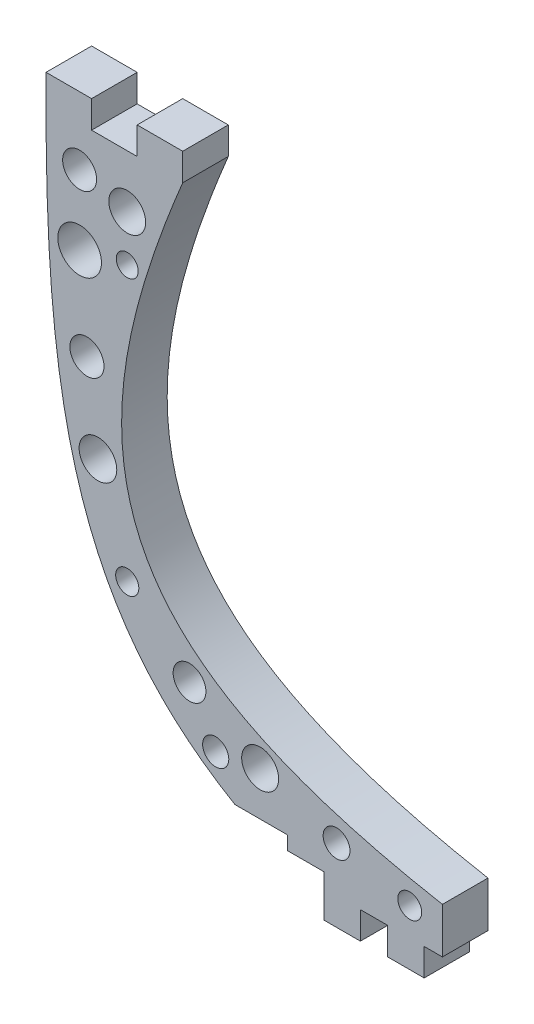
SolidWorks part; units mm, degrees
ref_plane "Plan de face" through (0, 0, 0) normal (0, 0, 1) x (1, 0, 0)
ref_plane "Plan de dessus" through (0, 0, 0) normal (0, 1, 0) x (1, 0, 0)
ref_plane "Plan de droite" through (0, 0, 0) normal (1, 0, 0) x (0, 0, -1)
sketch "Esquisse3" plane through (0, 0, 0) normal (0, 0, 1) x (1, 0, 0)
  line L0 (-7.5, 57.73) -> (-7.5, 0) construction
  line L1 (7.5, 57.73) -> (7.5, 17.682) construction
  line L2 (30, -4.6) -> (30, -1.6)
  line L3 (34, -4.6) -> (30, -4.6)
  line L4 (30, -1.6) -> (27, -1.6)
  line L5 (27, -1.6) -> (27, -4.6)
  line L6 (27, 0) -> (-7.5, 0) construction
  line L7 (7.5, 17.682) -> (36, 3.4) construction
  line L8 (34, -4.6) -> (34, -1.6)
  line L9 (34, -1.6) -> (36, -1.6)
  line L10 (36, -1.6) -> (36, 3.4)
  line L11 (27, -4.6) -> (23, -4.6)
  line L12 (16, 0) -> (-7.5, 11.7764) construction
  line L13 (-7.5, 11.7764) -> (-7.5, 57.73) construction
  line L14 (23, -4.6) -> (23, 0)
  line L15 (-7.5, 93.6282) -> (-7.5, 21.7981) construction
  line L16 (0.2936, 7.8708) -> (32.1661, -8.1012) construction
  line L17 (23, 0) -> (16, 0)
  circle A0 centre (-3.8151, 53.3093) radius 1.8639
  circle A1 centre (1.412, 51.9307) radius 2.0235
  circle A2 centre (-3.8151, 45.6697) radius 2.394
  circle A3 centre (1.412, 46.8759) radius 1.2063
  circle A4 centre (-3.0109, 35.9622) radius 1.8701
  circle A5 centre (-1.8047, 26.8291) radius 2.0679
  circle A6 centre (1.412, 16.777) radius 1.2715
  circle A7 centre (8.2475, 10.6309) radius 1.7991
  circle A8 centre (11.1195, 5.4612) radius 1.436
  circle A9 centre (16, 6.3228) radius 2.0318
  circle A10 centre (24.3837, 3.4) radius 1.4725
  circle A11 centre (32.4136, 1.4916) radius 1.3116
  spline S0 degree 3 poles (16, 0) (-3.9203, 9.9825) (-7.5, 27.8008) (-7.5, 57.73) knots 0 0 0 0 1 1 1 1
  spline S1 degree 3 poles (36, 3.4) (-1.2755, 10.2128) (-5.5671, 26.4267) (7.5, 57.73) knots 0 0 0 0 1 1 1 1
  point P45 (0, 0)
  point P46 (21.2334, 4.0781)
  point P47 (16, -0.1603)
  point P48 (17.1268, 2.4748)
  point P49 (24.3837, 3.4)
  point P50 (19.7989, 3.4)
  point P51 (32.4136, 1.4916)
  line B0 (0, 57.73) -> (0, 44.4605) construction
  line B1 (0, 57.73) -> (2.5, 57.73)
  line B2 (2.5, 60.73) -> (7.5, 60.73)
  line B3 (7.5, 60.73) -> (7.5, 57.73)
  line B4 (2.5, 60.73) -> (2.5, 57.73)
  line B5 (0, 57.73) -> (-2.5, 57.73)
  line B6 (-2.5, 57.73) -> (-2.5, 60.73)
  line B7 (-2.5, 60.73) -> (-7.5, 60.73)
  line B8 (-7.5, 60.73) -> (-7.5, 57.73)
  dimension "D9" = 1.6
  dimension "D1" = 3
  dimension "D2" = 4
  dimension "D3" = 2
  dimension "D4" = 3
  dimension "D5" = 1.6
  dimension "D6" = 5
  dimension "D7" = 30
  dimension "D8" = 12
  dimension "D10" = 57.73
sketch_block_instance "Insert M3 plots ep 5mm-3"
sketch_block "Insert M3 plots ep 5mm" parameters "D1"=5, "D2"=5, "D3"=3
extrude "Boss.-Extru.1" add sketch "Esquisse3" along normal blind 5 contours B5 B6 B7 B8 L0 L1 B3 B2 B4 B1 region at (30.7849, -3.1, 0)
sketch "Esquisse4" plane through (0, 0, 5) normal (0, 0, 1) x (1, 0, 0)
  line L0 (23, 0) -> (16, 0) construction
  line L1 (19, 0) -> (13.2295, 0)
  line L2 (19, 0) -> (19, 1.5)
  line L3 (19, 1.5) -> (13.2295, 1.5)
  line L4 (13.2295, 0) -> (13.2295, 1.5)
  line L5 (23, -4.6) -> (23, 0) construction
  spline S0 degree 3 poles (16, 0) (-3.9203, 9.9825) (-7.5, 27.8008) (-7.5, 57.73) knots 0 0 0 0 1 1 1 1 construction
  point P8 (12.6299, 1.5)
  dimension "D1" = 1.5
  dimension "D2" = 4
extrude "Enlèv. mat.-Extru.1" cut sketch "Esquisse4" against normal through all
